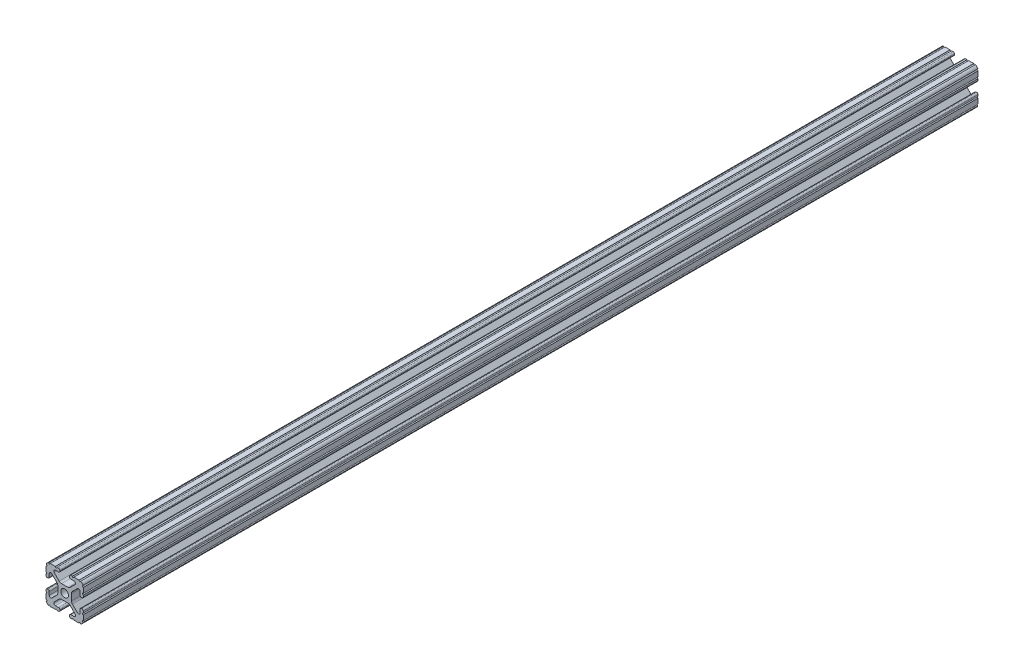
SolidWorks part; units mm, degrees
ref_plane "Front Plane" through (0, 0, 0) normal (0, 0, 1) x (1, 0, 0)
ref_plane "Top Plane" through (0, 0, 0) normal (0, 1, 0) x (1, 0, 0)
ref_plane "Right Plane" through (0, 0, 0) normal (1, 0, 0) x (0, 0, -1)
sketch "Sketch2" plane through (0, 0, 0) normal (0, 0, 1) x (1, 0, 0)
  line L0 (0, 12.7) -> (0, -12.7) construction
  line L1 (-12.7, 0) -> (12.7, 0) construction
  line L2 (3.2512, -12.7) -> (12.7, -12.7)
  line L3 (12.7, -12.7) -> (12.7, -3.2512)
  line L4 (3.2512, -12.7) -> (3.2512, -10.4902)
  line L5 (3.2512, -10.4902) -> (8.9276, -10.4902)
  line L6 (8.9276, -10.4902) -> (3.0856, -4.6482)
  line L7 (0, 0) -> (12.7, -12.7) construction
  line L8 (12.7, -3.2512) -> (10.4902, -3.2512)
  line L9 (10.4902, -3.2512) -> (10.4902, -8.9276)
  line L10 (10.4902, -8.9276) -> (4.6482, -3.0856)
  circle A0 centre (0, 0) radius 2.6035
  arc A1 (6.3485, -10.4902) -> (7.1039, -8.6665) centre (6.3485, -9.4219) ccw construction
  point P8 (0, -4.6482)
  dimension "Center Hole Diameter" = 5.207
  dimension "Rail Height" = 25.4
  dimension "Rail Width" = 25.4
  dimension "T-Slot Width" = 6.5024
  dimension "Slot Inner Width" = 14.8336
  dimension "Thickness" = 2.2098
  dimension "Slot Depth" = 5.842
  dimension "D1" = 2.2098
sketch "Sketch3" plane through (0, 0, 0) normal (1, 0, 0) x (0, 0, -1)
  line L0 (-304.8, -12.7) -> (304.8, -12.7) construction
  line L1 (-279.4, 0) -> (279.4, 0) construction
  dimension "Length" = 609.6
  dimension "D1" = 25.4
sketch "Sketch4" plane through (0, 0, 0) normal (0, 0, 1) x (1, 0, 0)
  line L0 (4.1904, -12.7) -> (10.1173, -12.7)
  line L1 (3.2512, -12.7) -> (12.7, -12.7) construction
  line L2 (3.2512, -12.7) -> (3.2512, -10.4902) construction
  line L3 (3.2512, -10.4902) -> (8.9276, -10.4902) construction
  line L4 (3.2512, -11.4294) -> (3.2512, -11.7608)
  line L5 (4.1904, -10.4902) -> (6.3485, -10.4902)
  line L6 (0, -4.6482) -> (2.164, -4.6482)
  line L7 (8.9276, -10.4902) -> (3.0856, -4.6482) construction
  line L8 (3.7373, -5.2999) -> (7.1039, -8.6665)
  line L9 (12.7, -12.7) -> (12.7, -3.2512) construction
  line L10 (10.4902, -8.9276) -> (4.6482, -3.0856) construction
  line L11 (10.4902, -3.2512) -> (10.4902, -8.9276) construction
  line L12 (10.4902, -6.3485) -> (10.4902, -4.1904)
  line L13 (12.7, -3.2512) -> (10.4902, -3.2512) construction
  line L14 (11.4294, -3.2512) -> (11.7608, -3.2512)
  line L15 (12.7, -4.1904) -> (12.7, -10.1173)
  line L16 (8.6665, -7.1039) -> (5.2999, -3.7373)
  line L17 (4.6482, 0) -> (4.6482, -2.164)
  line L18 (-12.7, 0) -> (12.7, 0) construction
  line L19 (0, -4.6482) -> (0, -2.6035)
  line L20 (0, 12.7) -> (0, -12.7) construction
  line L21 (4.6482, 0) -> (2.6035, 0)
  arc A0 (3.2512, -11.7608) -> (4.1904, -12.7) centre (4.1904, -11.7608) ccw
  arc A2 (3.2512, -11.4294) -> (4.1904, -10.4902) centre (4.1904, -11.4294) cw
  arc A3 (6.3485, -10.4902) -> (7.1039, -8.6665) centre (6.3485, -9.4219) ccw
  arc A4 (2.164, -4.6482) -> (3.7373, -5.2999) centre (2.164, -6.8732) cw
  arc A5 (10.1173, -12.7) -> (12.7, -10.1173) centre (10.1173, -10.1173) ccw
  arc A6 (8.6665, -7.1039) -> (10.4902, -6.3485) centre (9.4219, -6.3485) ccw
  arc A7 (10.4902, -4.1904) -> (11.4294, -3.2512) centre (11.4294, -4.1904) cw
  arc A8 (11.7608, -3.2512) -> (12.7, -4.1904) centre (11.7608, -4.1904) cw
  arc A9 (5.2999, -3.7373) -> (4.6482, -2.164) centre (6.8732, -2.164) cw
  circle A10 centre (0, 0) radius 2.6035 construction
  arc A11 (0, -2.6035) -> (2.6035, 0) centre (0, 0) ccw
  dimension "D1" = 2.5827
  dimension "D2" = 2.225
  dimension "D3" = 0.9392
extrude "Boss-Extrude1" add sketch "Sketch4" along normal mid plane 609.6
sketch "Sketch5" plane through (0, 0, 0) normal (0, 0, 1) x (1, 0, 0)
  line L0 (3.2512, -12.7) -> (12.7, -12.7) construction
  line L1 (4.1904, -10.4902) -> (6.3485, -10.4902) construction
  line L3 (0, 0) -> (12.7, -12.7) construction
  line L4 (6.3485, -10.4902) -> (6.3485, -12.7) construction
  line L5 (8.9276, -10.4902) -> (3.0856, -4.6482) construction
  circle A0 centre (10.3562, -12.7) radius 0.5524
  circle A1 centre (5.796, -12.7) radius 0.5524
  circle A2 centre (12.7, -10.3562) radius 0.5524
  circle A3 centre (12.7, -5.796) radius 0.5524
  point P10 (5.2694, -10.4902)
  point P12 (9.4219, -6.3485)
  dimension "D1" = 1.1049
extrude "Cut-Extrude1" cut sketch "Sketch5" against normal through all both and the other way through all
mirror "Mirror1" about plane through (0, 0, 0) normal (1, 0, 0) of bodies 137 134
mirror "Mirror2" about plane through (0, 0, 0) normal (0, 1, 0) of bodies 135
sketch "Sketch6" plane through (0, 4.6482, 0) normal (0, 1, 0) x (1, 0, 0)
  line L0 (-2.164, 304.8) -> (2.164, 304.8) construction
  line L1 (0, 192.7723) -> (0, -328.799) construction
  line L3 (0, 304.8) -> (0, 192.7723) construction
  circle A0 centre (0, 254) radius 2.6035
  circle A1 centre (0, 177.8) radius 2.6035
  circle A2 centre (0, -152.4) radius 2.6035
  dimension "D1" = 5.207
  dimension "D3" = 5.207
  dimension "D5" = 5.207
  dimension "D2" = 50.8
  dimension "D4" = 76.2
  dimension "D6" = 330.2
extrude "Cut-Extrude2" cut sketch "Sketch6" against normal blind 71.628 and the other way blind 31.496
equation "\"D1@Boss-Extrude1\"=\"Length@Sketch3\""
equation "\"D1@Sketch2\"=\"Thickness@Sketch2\""
equation "\"D2@Sketch4\"=\"Slot Inner Width@Sketch2\"*0.15"
equation "\"D1@Sketch4\"=\"D3@Sketch4\"*2.75"
equation "\"D3@Sketch4\"=\"Thickness@Sketch2\"*0.425"
equation "\"D1@Sketch5\"=\"Thickness@Sketch2\"*0.5"
